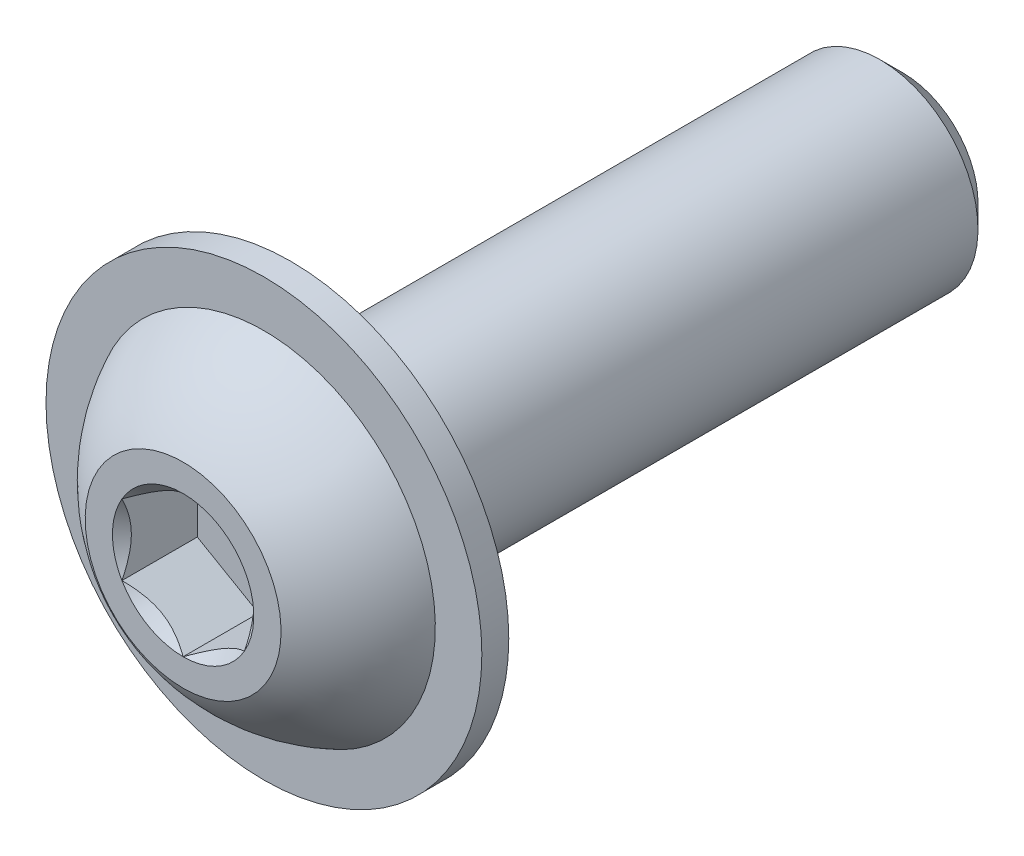
SolidWorks part; units mm, degrees
material "AISI 304"
ref_plane "Front" through (0, 0, 0) normal (0, 0, 1) x (1, 0, 0)
ref_plane "Top" through (0, 0, 0) normal (0, 1, 0) x (1, 0, 0)
ref_plane "Right" through (0, 0, 0) normal (1, 0, 0) x (0, 0, -1)
sketch "Sketch1" plane through (0, 0, 0) normal (1, 0, 0) x (0, 0, -1)
  line L2 (4.4, 4) -> (29.4, 4)
  line L3 (29.4, 4) -> (29.4, 0)
  line L4 (29.4, 0) -> (4.4, 0)
  line L6 (3.3, 7) -> (4.4, 7) construction
  line L7 (29.4, 4) -> (29.4, -4) construction
  line L8 (0, 0) -> (4.4, 0) construction
  line L9 (4.4, 7) -> (4.4, -7) construction
  line L11 (4.4, 4) -> (4.4, 0)
  line L13 (0, 2.5) -> (0, -2.5) construction
  line L14 (0, 2.5) -> (0, 4) construction
  line L15 (3.3, 7) -> (3.3, 8.9) construction
  line L16 (3.3, 8.9) -> (4.4, 8.9) construction
  line L17 (4.4, 8.9) -> (4.4, 7) construction
  line L18 (4.4, 8.9) -> (4.4, -8.9) construction
  arc A3 (0, 4) -> (3.3, 7) centre (6.65, 0) cw construction
  dimension "D1" = 1.1
revolve "Revolve1" add sketch "Sketch1" angle 360 mid plane about L4
sketch "Sketch3" plane through (0, 0, -29.4) normal (0, 0, -1) x (-1, 0, 0)
  circle A0 centre (0, 0) radius 4
curve "Helix/Spiral1" pitch 1.25 height 26.25 turns 21
sketch "Sketch2" plane through (0, 0, 0) normal (1, 0, 0) x (0, 0, -1)
  line L0 (29.4, 4) -> (30.4937, 4)
  line L1 (30.4937, 4) -> (30.025, 3.1881)
  line L2 (30.025, 3.1881) -> (29.8687, 3.1881)
  line L3 (29.8687, 3.1881) -> (29.4, 4)
  line L4 (29.6344, 3.5941) -> (30.2594, 3.5941) construction
  dimension "D1" = 60
  dimension "D2" = 0.1562
  dimension "D3" = 0.625
chamfer "Chamfer1" distance 0.9375 angle 45 1 edges at (0, 4, -29.4)
sweep "Cut-Sweep1" [suppressed] cut profiles "Sketch2" path "Helix/Spiral1"
sketch "Sketch7" plane through (0, 0, 0) normal (1, 0, 0) x (0, 0, -1)
  line L6 (3.3, 7) -> (4.4, 7) construction
  line L8 (0, 0) -> (4.4, 0) construction
  line L11 (4.4, 7) -> (4.4, -7) construction
  line L12 (3.3, 7) -> (4.4, 7)
  line L13 (0, 0) -> (4.4, 0)
  line L14 (0, 2.5) -> (0, -2.5) construction
  line L15 (4.4, 7) -> (4.4, 0)
  line L16 (0, 4) -> (0, 0)
  arc A2 (3.3, 7) -> (0, 4) centre (6.65, 0) ccw construction
  arc A3 (3.3, 7) -> (0, 4) centre (6.65, 0) ccw
revolve "Revolve2" add sketch "Sketch7" angle 360 mid plane about L13
sketch "Sketch11" plane through (0, 0, -4.4) normal (0, 0, -1) x (-1, 0, 0)
  circle A0 centre (0, 0) radius 8.9
extrude "Boss-Extrude3" add sketch "Sketch11" against normal up to vertex (1.1 mm away) up to point (0, 7, -3.3)
sketch "Sketch5" plane through (0, 0, 0) normal (0, 0, 1) x (1, 0, 0)
  line L1 (2.5, -1.4434) -> (2.5, 1.4434)
  line L2 (2.5, 1.4434) -> (0, 2.8868)
  line L3 (0, 2.8868) -> (-2.5, 1.4434)
  line L4 (-2.5, 1.4434) -> (-2.5, -1.4434)
  line L5 (-2.5, -1.4434) -> (0, -2.8868)
  line L6 (0, -2.8868) -> (2.5, -1.4434)
  circle A0 centre (0, 0) radius 2.5 construction
extrude "Cut-Extrude2" cut sketch "Sketch5" against normal blind 3.08
sketch "Sketch6" plane through (0, 0, 0) normal (0, 0, 1) x (1, 0, 0)
  circle A0 centre (0, 0) radius 2.8868
extrude "Cut-Extrude3" cut sketch "Sketch6" against normal blind 3.08 draft 45
sketch "Sketch9" [suppressed] plane through (0, 0, -5.0546) normal (0, 0, 1) x (1, 0, 0)
  circle A2 centre (0, 0) radius 4.7625
extrude "Boss-Extrude2" [suppressed] add sketch "Sketch9" against normal offset from surface (6.35 mm away) 31.75
sketch "Sketch10" plane through (0, 0, 0) normal (1, 0, 0) x (0, 0, -1)
  line L0 (29.4, 4) -> (29.4, -4) construction
  point P0 (27.525, -4)
  dimension "D1" = 1.875
equation "\"D3@Helix/Spiral1\" = \"Lg@Sketch1\" + \"D4@Helix/Spiral1\""
equation "\"D2@Sketch2\" = \"D4@Helix/Spiral1\" * .125"
equation "\"D3@Sketch2\" = \"D4@Helix/Spiral1\" * .5"
equation "\"D1@Chamfer1\" = \"D4@Helix/Spiral1\" * .75"
equation "\"D1@Cut-Extrude2\" = \"Head Ht@Sketch1\" * .7"
equation "\"D1@Sketch1\" = \"Head Ht@Sketch1\" * .25"
equation "\"D1@Sketch10\" = \"D4@Helix/Spiral1\" * 1.5"
equation "\"D1@Cut-Extrude3\" = \"D1@Cut-Extrude2\""
